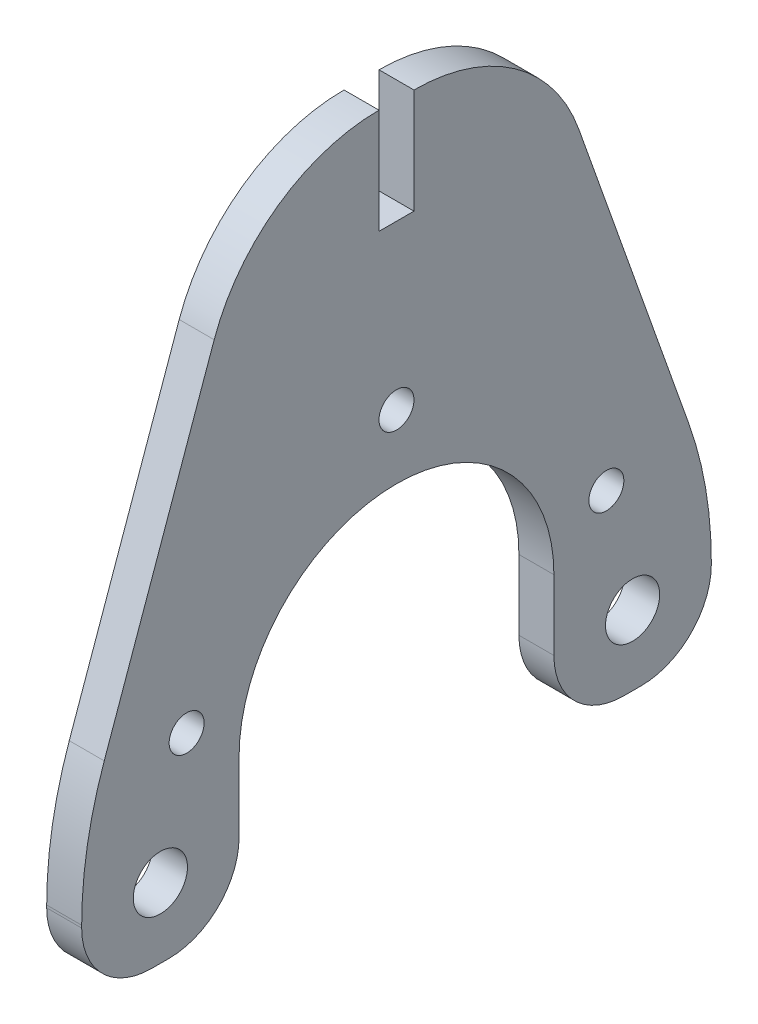
SolidWorks part; units mm, degrees
material "6061 Alloy"
ref_plane "Front Plane" through (0, 0, 0) normal (0, 0, 1) x (1, 0, 0)
ref_plane "Top Plane" through (0, 0, 0) normal (0, 1, 0) x (1, 0, 0)
ref_plane "Right Plane" through (0, 0, 0) normal (1, 0, 0) x (0, 0, -1)
sketch "Sketch1" plane through (0, 0, 0) normal (1, 0, 0) x (0, 0, -1)
  line L0 (1.5875, 44.45) -> (1.5875, 34.925)
  line L1 (1.5875, 34.925) -> (-1.5875, 34.925)
  line L2 (0, 0) -> (0, 73.524) construction
  line L3 (-1.5875, 44.45) -> (-1.5875, 34.925)
  line L4 (21.4312, -6.35) -> (-21.4312, -6.35) construction
  line L5 (16.5481, 33.885) -> (28.575, 0)
  line L6 (-16.5481, 33.885) -> (-28.575, 0)
  line L7 (28.575, 0) -> (28.575, -12.7)
  line L8 (28.575, -12.7) -> (14.2875, -12.7)
  line L9 (14.2875, -12.7) -> (14.2875, 0)
  line L10 (-14.2875, 0) -> (-14.2875, -12.7)
  line L11 (-14.2875, -12.7) -> (-28.575, -12.7)
  line L12 (-28.575, -12.7) -> (-28.575, 0)
  arc A0 (14.2875, 0) -> (-14.2875, 0) centre (0, 0) ccw
  arc A5 (16.5481, 33.885) -> (1.5875, 44.45) centre (1.5875, 28.575) ccw
  arc A10 (-16.5481, 33.885) -> (-1.5875, 44.45) centre (-1.5875, 28.575) cw
  circle A11 centre (21.4312, -6.35) radius 2.5797 construction
  circle A12 centre (-21.4312, -6.35) radius 2.5797 construction
  point P1 (0, -6.35)
  point P8 (-29.1435, 11.9572)
  point P9 (21.4312, -12.7)
  point P18 (0, 34.925)
  point P22 (28.575, 1.0004)
  point P24 (0, 0)
  dimension "D1" = 28.575
  dimension "D3" = 57.15
  dimension "D4" = 15.875
  dimension "D5" = 12.7
  dimension "D6" = 42.8625
  dimension "D7" = 14.2875
  dimension "D9" = 5.1594
  dimension "D2" = 3.175
  dimension "D10" = 6.35
  dimension "D12" = 9.525
extrude "Boss-Extrude1" add sketch "Sketch1" along normal blind 3.175
hole_wizard "#10 (0.1935) Diameter Hole1" positions "Sketch2" profile "Sketch3" hole size "#10" standard "ANSI Inch"
sketch "Sketch2" plane through (0, 0, 0) normal (-1, 0, 0) x (0, 0, 1)
  line L2 (-21.4312, -6.35) -> (21.4312, -6.35) construction
  point P0 (-21.4312, -6.35)
  point P2 (21.4312, -6.35)
  point P29 (0, -6.35)
  dimension "D1" = 42.8625
  dimension "D2" = 6.35
sketch "Sketch3" plane through (0, -6.35, -21.4312) normal (0, 1, 0) x (0, 0, 1)
  line L0 (0, 0) -> (0, 20.4786)
  line L1 (0, 20.4786) -> (2.4574, 19.002)
  line L2 (2.4574, 19.002) -> (2.4574, 0)
  line L5 (2.4574, 0) -> (0, 0)
  line L10 (0, 20.4786) -> (-2.4574, 19.002) construction
  line L11 (0, -6.35) -> (0, 107.95) construction
  dimension "Hole Dia." = 4.9149
  dimension "Hole Depth" = 19.002
  dimension "Drill Angle" = 118
sketch "Sketch4" plane through (3.175, 0, 0) normal (1, 0, 0) x (0, 0, -1)
  circle A6 centre (0, 20.0978) radius 1.5875 construction
  circle A7 centre (0, 20.0978) radius 1.5875
  circle A8 centre (-19.0489, 4.2227) radius 1.5875 construction
  circle A9 centre (-19.0489, 4.2227) radius 1.5875
  circle A10 centre (19.0489, 4.2228) radius 1.5875 construction
  circle A11 centre (19.0489, 4.2228) radius 1.5875
  point P9 (0, 0)
  point P10 (0, 0)
extrude "Cut-Extrude1" cut sketch "Sketch4" against normal through all
fillet "Fillet2" radius 35.56 2 edges at (1.5875, 0, 28.575) (1.5875, 0, -28.575)
fillet "Fillet1" radius 6.35 4 edges at (1.5875, -12.7, -28.575) (1.5875, -12.7, -14.2875) (1.5875, -12.7, 28.575) (1.5875, -12.7, 14.2875)
